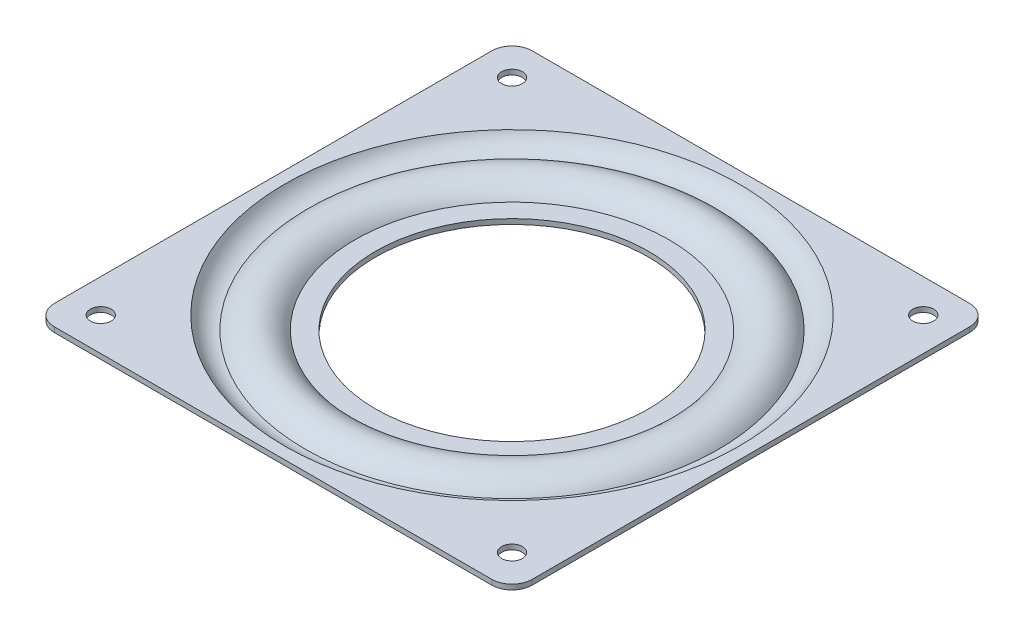
SolidWorks part; units mm, degrees
ref_plane "前视基准面" through (0, 0, 0) normal (0, 0, 1) x (1, 0, 0)
ref_plane "上视基准面" through (0, 0, 0) normal (0, 1, 0) x (1, 0, 0)
ref_plane "右视基准面" through (0, 0, 0) normal (1, 0, 0) x (0, 0, -1)
sketch "草图1" plane through (0, 0, 0) normal (0, 0, 1) x (1, 0, 0)
  line L0 (-36.7805, 0) -> (-35.9228, 0)
  line L1 (0, 6.9172) -> (0, -6.9172) construction
  line L2 (-31, -2.5698) -> (-27, -2.5698)
  line L3 (-35.9228, 0) -> (0, 0) construction
  line L4 (0, 0) -> (43.3864, 0) construction
  line L5 (-43.3864, 0) -> (-36.7805, 0) construction
  line L6 (-31.5531, -3.5698) -> (-27, -3.5698)
  line L7 (-27, -2.5698) -> (-27, -3.5698)
  line L8 (-44.9105, 0) -> (-45.8139, -0.4289)
  arc A0 (-44.9105, 0) -> (-40.8455, -2.5698) centre (-40.8455, 1.9302) ccw
  arc A1 (-40.8455, -2.5698) -> (-31, -2.5698) centre (-35.9228, -6) cw
  arc A2 (-40.8455, -2.5698) -> (-36.8127, -0.0664) centre (-40.8455, 1.9302) ccw construction
  arc A3 (-36.8127, -0.0664) -> (-36.7805, 0) centre (-40.8455, 1.9302) ccw
  arc A4 (-45.8139, -0.4289) -> (-40.2759, -3.5402) centre (-40.8455, 1.9302) ccw
  arc A5 (-40.2759, -3.5402) -> (-31.5531, -3.5698) centre (-35.9228, -6) cw
  point P4 (0, 0)
  point P8 (0, 0)
  dimension "D1" = 4.5
  dimension "D2" = 6
  dimension "D3" = 27
  dimension "D4" = 4
revolve "旋转1" add sketch "草图1" angle 360 about L1 region at (-33.2348, -0.8509, 0)
sketch "草图2" plane through (0, 0, 0) normal (0, 1, 0) x (1, 0, 0)
  line L0 (0, 0) -> (-40.6586, 40.6586) construction
  line L1 (-43.25, 47.25) -> (47.25, 47.25)
  line L2 (-47.25, 43.25) -> (-47.25, -47.25)
  line L3 (-47.25, -47.25) -> (47.25, -47.25)
  line L4 (47.25, 47.25) -> (47.25, -47.25)
  line L5 (-47.25, 47.25) -> (47.25, -47.25) construction
  line L6 (-47.25, -47.25) -> (47.25, 47.25) construction
  line L7 (0, 0) -> (40.6586, 40.6586) construction
  line L8 (0, 0) -> (-43.25, 43.25) construction
  circle A0 centre (0, 0) radius 44.9105 construction
  circle A1 centre (0, 0) radius 44.9105
  arc A2 (-43.25, 47.25) -> (-47.25, 43.25) centre (-43.25, 43.25) ccw
  circle A3 centre (-40.6586, 40.6586) radius 2.05
  circle A4 centre (40.6586, 40.6586) radius 2.05
  circle A5 centre (40.6586, -40.6586) radius 2.05
  circle A6 centre (-40.6586, -40.6586) radius 2.05
  arc A7 (47.25, 43.25) -> (43.25, 47.25) centre (43.25, 43.25) ccw
  arc A8 (43.25, -47.25) -> (47.25, -43.25) centre (43.25, -43.25) ccw
  arc A9 (-47.25, -43.25) -> (-43.25, -47.25) centre (-43.25, -43.25) ccw
  dimension "D3" = 4
  dimension "D4" = 4.1
  dimension "D9" = 4
  dimension "D1" = 94.5
  dimension "D2" = 94.5
  dimension "D5" = 57.5
  dimension "D7" = 90
  dimension "D8" = 57.5
  dimension "D10" = 61.1647
  dimension "D6" = 4
extrude "凸台-拉伸1" add sketch "草图2" against normal blind 1 contours L2 A9 L3 A8 L4 A7 L1 A2 A6 A5 A4 A3 A1 region at (0, 0, -45.9136)
